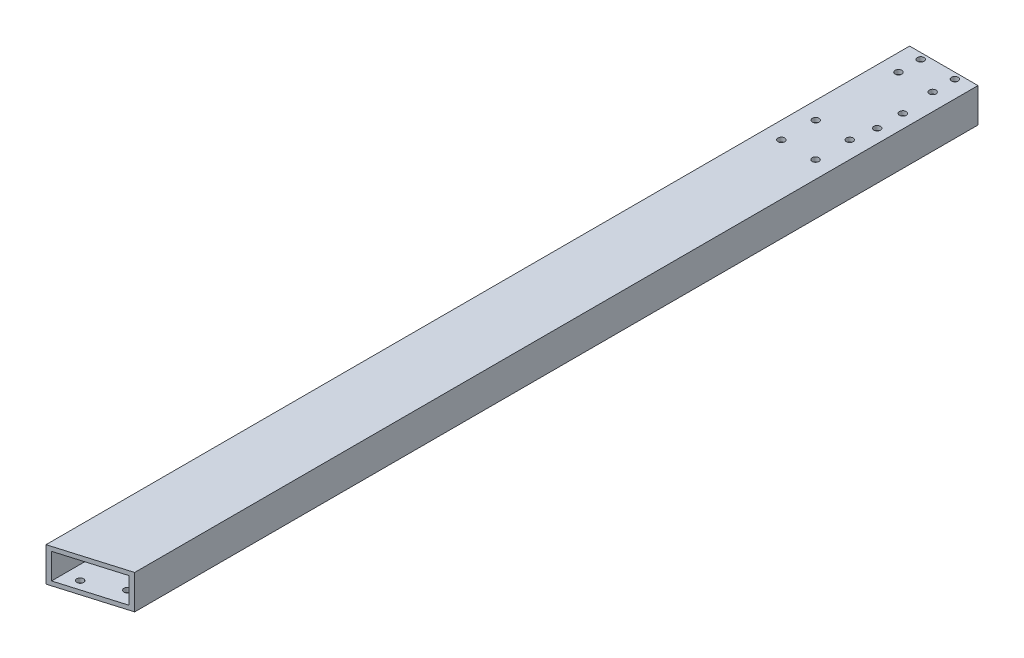
SolidWorks part; units mm, degrees
material "1060 Alloy"
ref_plane "Front Plane" through (0, 0, 0) normal (0, 0, 1) x (1, 0, 0)
ref_plane "Top Plane" through (0, 0, 0) normal (0, 1, 0) x (1, 0, 0)
ref_plane "Right Plane" through (0, 0, 0) normal (1, 0, 0) x (0, 0, -1)
sketch "Sketch1" plane through (0, 0, 0) normal (0, 0, 1) x (1, 0, 0)
  line L0 (-22.225, 9.525) -> (22.225, 9.525)
  line L2 (-25.4, 12.7) -> (25.4, 12.7)
  line L3 (-25.4, 12.7) -> (-25.4, -12.7)
  line L4 (-25.4, -12.7) -> (25.4, -12.7)
  line L5 (25.4, 12.7) -> (25.4, -12.7)
  line L10 (22.225, 9.525) -> (22.225, -9.525)
  line L11 (-22.225, -9.525) -> (22.225, -9.525)
  line L12 (-22.225, 9.525) -> (-22.225, -9.525)
  point P12 (0, 12.7)
  point P14 (25.4, 0)
  dimension "Wall Thickness" = 3.175
  dimension "Outside Width" = 50.8
  dimension "Outside Height" = 25.4
  dimension "Inside Height" = 19.05
  dimension "Inside Width" = 44.45
sketch "Sketch2" plane through (0, 0, 0) normal (1, 0, 0) x (0, 0, -1)
  line L0 (320.675, 0) -> (-320.675, 0)
  point P4 (0, 0)
  point P7 (-320.675, 0)
  point P10 (320.675, 0)
  dimension "Length" = 641.35
sketch "Sketch3" plane through (0, 0, 0) normal (0, 0, 1) x (1, 0, 0)
  line L21 (25.4, 12.7) -> (-25.4, 12.7)
  line L22 (25.4, -12.7) -> (25.4, 12.7)
  line L23 (-25.4, -12.7) -> (25.4, -12.7)
  line L24 (-25.4, 12.7) -> (-25.4, -12.7)
  line L25 (25.4, 12.7) -> (-25.4, 12.7)
  line L26 (25.4, -12.7) -> (25.4, 12.7)
  line L27 (-25.4, -12.7) -> (25.4, -12.7)
  line L28 (-25.4, 12.7) -> (-25.4, -12.7)
  line L29 (22.225, 9.525) -> (-22.225, 9.525)
  line L30 (22.225, -9.525) -> (22.225, 9.525)
  line L31 (-22.225, -9.525) -> (22.225, -9.525)
  line L32 (-22.225, 9.525) -> (-22.225, -9.525)
  line L33 (22.225, 9.525) -> (-22.225, 9.525)
  line L34 (22.225, -9.525) -> (22.225, 9.525)
  line L35 (-22.225, -9.525) -> (22.225, -9.525)
  line L36 (-22.225, 9.525) -> (-22.225, -9.525)
  dimension "D1" = 0
  dimension "D2" = 0
extrude "Boss-Extrude1" add sketch "Sketch3" along normal up to vertex (320.675 mm away) and the other way up to vertex (320.675 mm away) up to point (0, 0, 320.675) other way up to point (0, 0, -320.675)
sketch "Drawing Reference" plane through (0, 0, 0) normal (1, 0, 0) x (0, 0, -1)
  line L0 (-320.675, 0) -> (320.675, 0) construction
  line L1 (0, -12.7) -> (0, 12.7) construction
  line L2 (-320.675, -12.7) -> (320.675, -12.7) construction
  line L5 (-320.675, 12.7) -> (320.675, 12.7) construction
  point P7 (-284.099, 0)
  point P8 (284.099, 0)
  dimension "D1" = 36.576
sketch "Sketch4" plane through (0, 12.7, 0) normal (0, 1, 0) x (1, 0, 0)
  line L0 (-25.4, -320.675) -> (25.4, -305.6274)
  line L1 (25.4, -320.675) -> (25.4, 320.675) construction
  line L2 (25.4, -320.675) -> (-25.4, -320.675)
  dimension "D1" = 16.5
extrude "Cut-Extrude1" cut sketch "Sketch4" against normal through all and the other way through all flip side to cut
sketch "Sketch6" plane through (0, -12.7, 0) normal (0, -1, 0) x (1, 0, 0)
  line L0 (25.4, 305.6274) -> (22.1108, 294.5233) construction
  line L1 (25.4, 279.2824) -> (22.225, 279.2824) construction
  line L2 (25.4, 305.6274) -> (25.4, -320.675) construction
  line L3 (22.225, 279.2824) -> (22.225, 313.1512) construction
  line L4 (22.1108, 294.5233) -> (11.811, 297.5742) construction
  line L5 (-11.811, 250.3501) -> (-11.811, 328.3651) construction
  line L6 (-25.4, 320.675) -> (-27.5213, 313.5136) construction
  line L7 (-25.4, 287.6223) -> (-22.225, 287.6223) construction
  line L8 (-25.4, 320.675) -> (-25.4, -320.675) construction
  line L9 (-22.225, 287.6223) -> (-22.225, 328.3651) construction
  line L10 (-27.5213, 313.5136) -> (-11.811, 308.86) construction
  line L11 (11.811, 250.3501) -> (11.811, 313.1512) construction
  line L12 (-27.5213, 313.5136) -> (-36.5388, 283.071) construction
  line L13 (22.1108, 294.5233) -> (13.0933, 264.0807) construction
  line L14 (-37.6746, 250.3501) -> (48.6057, 250.3501) construction
  line L15 (-11.811, 287.6223) -> (-11.811, 328.3651) construction
  line L16 (11.811, 279.2824) -> (11.811, 313.1512) construction
  line L17 (-36.5388, 283.071) -> (-11.811, 275.7463) construction
  line L18 (13.0933, 264.0807) -> (11.811, 264.4606) construction
  dimension "D1" = 10.414
  dimension "D2" = 10.414
hole_wizard "#10 Clearance Hole1" positions "Sketch7" profile "Sketch8" hole size "#10" standard "ANSI Inch"
sketch "Sketch7" plane through (0, -12.7, 0) normal (0, -1, 0) x (-1, 0, 0)
  point P0 (-11.811, -264.4606)
  point P3 (11.811, -275.7463)
  point P7 (-11.811, -297.5742)
  point P10 (11.811, -308.86)
sketch "Sketch8" plane through (11.811, -12.7, 264.4606) normal (1, 0, 0) x (0, 0, -1)
  line L0 (0, 0) -> (0, 6.5757)
  line L1 (0, 6.5757) -> (2.4892, 5.08)
  line L2 (2.4892, 5.08) -> (2.4892, 0)
  line L5 (2.4892, 0) -> (0, 0)
  line L10 (0, 6.5757) -> (-2.4892, 5.08) construction
  line L11 (0, -6.35) -> (0, 107.95) construction
  dimension "Hole Dia." = 4.9784
  dimension "Hole Depth" = 5.08
  dimension "Drill Angle" = 118
sketch "Sketch9" plane through (0, 12.7, 0) normal (0, 1, 0) x (1, 0, 0)
  line L0 (-12.7, 316.23) -> (-10.16, 316.23) construction
  line L2 (-9.1044, 314.5662) -> (-9.0928, 314.5269) construction
  line L3 (10.16, 316.23) -> (12.7, 316.23) construction
  line L4 (12.7, 299.72) -> (10.16, 299.72) construction
  line L5 (-10.16, 299.72) -> (-12.7, 299.72) construction
hole_wizard "#10 Clearance Hole2" positions "Sketch10" profile "Sketch11" hole size "#10" standard "ANSI Inch"
sketch "Sketch10" plane through (0, 12.7, 0) normal (0, 1, 0) x (1, 0, 0)
  point P0 (12.7, 299.72)
  point P3 (-12.7, 299.72)
  point P6 (12.7, 316.23)
  point P9 (-12.7, 316.23)
sketch "Sketch11" plane through (12.7, 12.7, -299.72) normal (1, 0, 0) x (0, 0, 1)
  line L0 (0, 0) -> (0, 6.5757)
  line L1 (0, 6.5757) -> (2.4892, 5.08)
  line L2 (2.4892, 5.08) -> (2.4892, 0)
  line L5 (2.4892, 0) -> (0, 0)
  line L10 (0, 6.5757) -> (-2.4892, 5.08) construction
  line L11 (0, -6.35) -> (0, 107.95) construction
  dimension "Hole Dia." = 4.9784
  dimension "Hole Depth" = 5.08
  dimension "Drill Angle" = 118
sketch "Sketch12" plane through (0, 12.7, 0) normal (0, 1, 0) x (1, 0, 0)
  line L0 (-12.7, 238.125) -> (12.7, 238.125) construction
  line L1 (12.7, 238.125) -> (12.7, 212.725) construction
  line L2 (12.7, 212.725) -> (-12.7, 212.725) construction
  line L3 (-12.7, 212.725) -> (-12.7, 238.1868) construction
hole_wizard "#10 Clearance Hole3" positions "Sketch13" profile "Sketch14" hole size "#10" standard "ANSI Inch" end condition through all
sketch "Sketch13" plane through (0, 12.7, 0) normal (0, 1, 0) x (1, 0, 0)
  point P0 (-12.7, 212.725)
  point P3 (12.7, 212.725)
  point P6 (12.7, 238.125)
  point P9 (-12.5651, 238.125)
  point P12 (15.4075, 274.8363)
  point P15 (15.4075, 255.7863)
sketch "Sketch14" plane through (-12.7, 12.7, -212.725) normal (1, 0, 0) x (0, 0, 1)
  line L0 (0, 0) -> (0, 25.4)
  line L1 (0, 25.4) -> (2.4892, 25.4)
  line L2 (2.4892, 25.4) -> (2.4892, 0)
  line L5 (2.4892, 0) -> (0, 0)
  line L11 (0, -6.35) -> (0, 107.95) construction
  dimension "Thru Hole Dia." = 4.9784
  dimension "Thru Hole Depth" = 25.4
equation "\"D1@Drawing Reference\"=\"Outside Width@Sketch1\" * 0.72"
